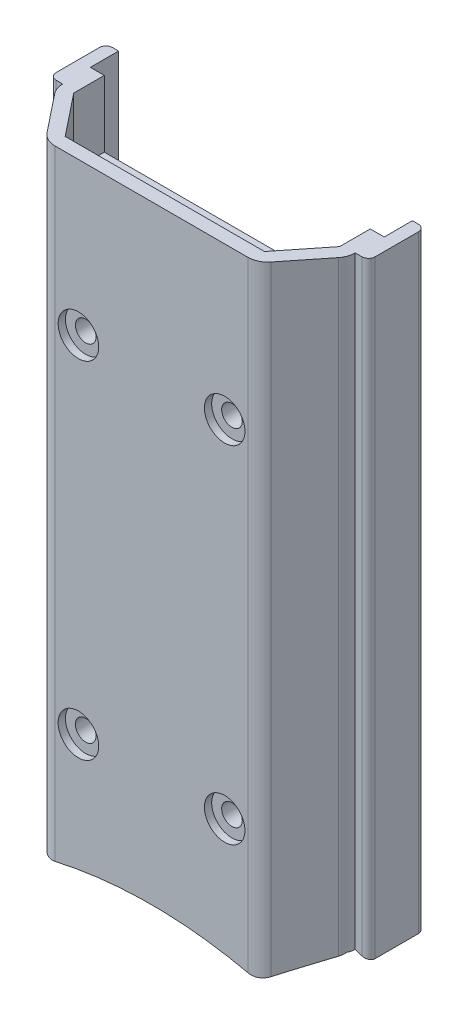
SolidWorks part; units mm, degrees
ref_plane "前视基准面" through (0, 0, 0) normal (0, 0, 1) x (1, 0, 0)
ref_plane "上视基准面" through (0, 0, 0) normal (0, 1, 0) x (1, 0, 0)
ref_plane "右视基准面" through (0, 0, 0) normal (1, 0, 0) x (0, 0, -1)
other "Configuration Table"
sketch "草图1" plane through (0, 0, 0) normal (0, 1, 0) x (1, 0, 0)
  line L5 (21.3466, -10.7196) -> (16.852, -16.3628)
  line L7 (20, -4.6001) -> (22, -4.6001)
  line L9 (20, -9.2001) -> (20, -4.6001)
  line L10 (14.9873, -15.4937) -> (20, -9.2001)
  line L11 (14.5054, -17.4937) -> (-14.5054, -17.4937)
  line L12 (-14.9873, -15.4937) -> (14.9873, -15.4937)
  line L14 (-20, -9.2001) -> (-14.9873, -15.4937)
  line L15 (-20, -4.6001) -> (-20, -9.2001)
  line L17 (-22.1, -0.3496) -> (-23, -0.3496)
  line L18 (-24, -1.3496) -> (-24, -7.8505)
  line L20 (-22, -4.6001) -> (-22.1, -4.6001)
  line L21 (-22.1, -4.6001) -> (-22.1, -0.3496)
  line L22 (22.1, -0.3496) -> (23, -0.3496)
  line L23 (24, -1.3496) -> (24, -7.8505)
  line L41 (22, -4.6001) -> (22.1, -4.6001)
  line L42 (22.1, -4.6001) -> (22.1, -0.3496)
  line L43 (-16.852, -16.3628) -> (-21.3466, -10.7196)
  line L57 (-22, -4.6001) -> (-20, -4.6001)
  line L59 (-22, -8.8505) -> (-23, -8.8505)
  line L61 (22, -8.8505) -> (23, -8.8505)
  arc A2 (23, -8.8505) -> (24, -7.8505) centre (23, -7.8505) ccw
  arc A3 (24, -1.3496) -> (23, -0.3496) centre (23, -1.3496) ccw
  arc A12 (16.852, -16.3628) -> (14.5054, -17.4937) centre (14.5054, -14.4937) cw
  arc A14 (-14.5054, -17.4937) -> (-16.852, -16.3628) centre (-14.5054, -14.4937) cw
  arc A16 (-23, -8.8505) -> (-24, -7.8505) centre (-23, -7.8505) cw
  arc A17 (-23, -0.3496) -> (-24, -1.3496) centre (-23, -1.3496) ccw
  arc A19 (21.3466, -10.7196) -> (22, -8.8505) centre (19, -8.8505) ccw
  arc A20 (-22, -8.8505) -> (-21.3466, -10.7196) centre (-19, -8.8505) ccw
  dimension "D3" = 0.1
  dimension "D2" = 0.1
extrude "凸台-拉伸1" add sketch "草图1" along normal up to surface (58.8974 mm away)
sketch "草图2" plane through (0, 0, 0) normal (0, -1, 0) x (1, 0, 0)
  line L18 (23, 8.8505) -> (22, 8.8505)
  line L19 (-24, 7.8505) -> (-24, 1.3496)
  line L20 (-23, 0.3496) -> (-22.1, 0.3496)
  line L21 (-22.1, 0.3496) -> (-22.1, 4.6001)
  line L22 (-22.1, 4.6001) -> (-20, 4.6001)
  line L23 (-20, 4.6001) -> (-20, 9.2001)
  line L24 (-20, 9.2001) -> (-14.9873, 15.4937)
  line L25 (-14.9873, 15.4937) -> (14.9873, 15.4937)
  line L26 (14.9873, 15.4937) -> (20, 9.2001)
  line L27 (20, 9.2001) -> (20, 4.6001)
  line L28 (20, 4.6001) -> (22.1, 4.6001)
  line L29 (22.1, 4.6001) -> (22.1, 0.3496)
  line L30 (22.1, 0.3496) -> (23, 0.3496)
  line L31 (24, 1.3496) -> (24, 7.8505)
  line L32 (23, 8.8505) -> (22, 8.8505)
  line L33 (21.3466, 10.7196) -> (16.852, 16.3628)
  line L34 (14.5054, 17.4937) -> (-14.5054, 17.4937)
  line L37 (-24, 7.8505) -> (-24, 1.3496)
  line L38 (-23, 0.3496) -> (-22.1, 0.3496)
  line L39 (-22.1, 0.3496) -> (-22.1, 4.6001)
  line L40 (-22.1, 4.6001) -> (-20, 4.6001)
  line L41 (-20, 4.6001) -> (-20, 9.2001)
  line L42 (-20, 9.2001) -> (-14.9873, 15.4937)
  line L43 (-14.9873, 15.4937) -> (14.9873, 15.4937)
  line L44 (14.9873, 15.4937) -> (20, 9.2001)
  line L45 (20, 9.2001) -> (20, 4.6001)
  line L46 (20, 4.6001) -> (22.1, 4.6001)
  line L47 (22.1, 4.6001) -> (22.1, 0.3496)
  line L48 (22.1, 0.3496) -> (23, 0.3496)
  line L49 (24, 1.3496) -> (24, 7.8505)
  line L51 (21.3466, 10.7196) -> (16.852, 16.3628)
  line L52 (14.5054, 17.4937) -> (-14.5054, 17.4937)
  line L57 (-16.852, 16.3628) -> (-21.3466, 10.7196)
  line L58 (-16.852, 16.3628) -> (-21.3466, 10.7196)
  line L61 (-22, 8.8505) -> (-23, 8.8505)
  line L62 (-22, 8.8505) -> (-23, 8.8505)
  arc A8 (-21.3466, 10.7196) -> (-22, 8.8505) centre (-19, 8.8505) ccw
  arc A9 (-21.3466, 10.7196) -> (-22, 8.8505) centre (-19, 8.8505) ccw
  arc A10 (22, 8.8505) -> (21.3466, 10.7196) centre (19, 8.8505) ccw
  arc A11 (22, 8.8505) -> (21.3466, 10.7196) centre (19, 8.8505) ccw
  arc A12 (-23, 8.8505) -> (-24, 7.8505) centre (-23, 7.8505) ccw
  arc A13 (-24, 1.3496) -> (-23, 0.3496) centre (-23, 1.3496) ccw
  arc A14 (23, 0.3496) -> (24, 1.3496) centre (23, 1.3496) ccw
  arc A15 (24, 7.8505) -> (23, 8.8505) centre (23, 7.8505) ccw
  arc A18 (16.852, 16.3628) -> (14.5054, 17.4937) centre (14.5054, 14.4937) ccw
  arc A19 (-14.5054, 17.4937) -> (-16.852, 16.3628) centre (-14.5054, 14.4937) ccw
  arc A22 (-23, 8.8505) -> (-24, 7.8505) centre (-23, 7.8505) ccw
  arc A23 (-24, 1.3496) -> (-23, 0.3496) centre (-23, 1.3496) ccw
  arc A24 (23, 0.3496) -> (24, 1.3496) centre (23, 1.3496) ccw
  arc A25 (24, 7.8505) -> (23, 8.8505) centre (23, 7.8505) ccw
  arc A28 (16.852, 16.3628) -> (14.5054, 17.4937) centre (14.5054, 14.4937) ccw
  arc A29 (-14.5054, 17.4937) -> (-16.852, 16.3628) centre (-14.5054, 14.4937) ccw
  dimension "D1" = 0
extrude "凸台-拉伸2" add sketch "草图2" along normal up to surface (38.3996 mm away)
ref_plane "基准面1" through (0, -38.3996, 0) normal (0, -1, 0) x (-1, 0, 0)
sketch "草图3" plane through (0, 0, 4.6001) normal (0, 0, -1) x (-1, 0, 0)
  line L0 (22.1, -38.3996) -> (22.1, -35.3996)
  line L1 (22.1, 58.8974) -> (22.1, -38.3996) construction
  line L2 (22.1, -35.3996) -> (-22.1, -35.3996)
  line L3 (-22.1, 58.8974) -> (-22.1, -38.3996) construction
  line L4 (-22.1, -35.3996) -> (-22.1, -38.3996)
  line L5 (-22.1, -38.3996) -> (22.1, -38.3996)
  dimension "D1" = 3
extrude "凸台-拉伸3" add sketch "草图3" against normal up to surface (12.8937 mm away) up to face at (0, 10.2489, 17.4937)
sketch "草图4" plane through (0, 0, 4.6001) normal (0, 0, -1) x (-1, 0, 0)
  line L0 (22.1, 38.8974) -> (-22.1, 38.8974)
  line L3 (22.1, 58.8974) -> (22.1, -38.3996) construction
  line L4 (22.1, 38.8974) -> (22.1, 35.8974)
  line L7 (-22.1, 58.8974) -> (-22.1, -38.3996) construction
  line L8 (-22.1, 38.8974) -> (-22.1, 35.8974)
  line L9 (-22.1, 35.8974) -> (22.1, 35.8974)
  dimension "D2" = 3
extrude "凸台-拉伸4" add sketch "草图4" against normal up to surface (12.8937 mm away) up to face at (0, -12.5754, 17.4937)
sketch "草图5" plane through (0, 38.8974, 0) normal (0, 1, 0) x (1, 0, 0)
  line L3 (-22, -8.8505) -> (-22.1, -8.8505)
  line L4 (-22.1, -8.8505) -> (-22.1, -17.4937)
  line L5 (-22.1, -17.4937) -> (-14.5054, -17.4937)
  line L7 (-22.1, -8.8505) -> (-22.1, -17.4937)
  line L8 (-22.1, -17.4937) -> (-14.5054, -17.4937)
  line L9 (14.5054, -17.4937) -> (22.1, -17.4937)
  line L10 (22.1, -17.4937) -> (22.1, -8.8505)
  line L11 (21.3466, -10.7196) -> (16.852, -16.3628)
  line L12 (14.5054, -17.4937) -> (22.1, -17.4937)
  line L13 (22.1, -17.4937) -> (22.1, -8.8505)
  line L14 (21.3466, -10.7196) -> (16.852, -16.3628)
  line L17 (-22, -8.8505) -> (-22.1, -8.8505)
  line L18 (-16.852, -16.3628) -> (-21.3466, -10.7196)
  line L19 (-16.852, -16.3628) -> (-21.3466, -10.7196)
  line L22 (22.1, -8.8505) -> (22, -8.8505)
  line L23 (22.1, -8.8505) -> (22, -8.8505)
  arc A2 (-22, -8.8505) -> (-21.3466, -10.7196) centre (-19, -8.8505) ccw
  arc A3 (-16.852, -16.3628) -> (-14.5054, -17.4937) centre (-14.5054, -14.4937) ccw
  arc A4 (-22, -8.8505) -> (-21.3466, -10.7196) centre (-19, -8.8505) ccw
  arc A5 (21.3466, -10.7196) -> (22, -8.8505) centre (19, -8.8505) ccw
  arc A6 (-16.852, -16.3628) -> (-14.5054, -17.4937) centre (-14.5054, -14.4937) ccw
  arc A9 (14.5054, -17.4937) -> (16.852, -16.3628) centre (14.5054, -14.4937) ccw
  arc A10 (21.3466, -10.7196) -> (22, -8.8505) centre (19, -8.8505) ccw
  arc A12 (14.5054, -17.4937) -> (16.852, -16.3628) centre (14.5054, -14.4937) ccw
  dimension "D1" = 0
  dimension "D2" = 0
extrude "切除-拉伸1" cut sketch "草图5" against normal up to surface (77.297 mm away) contours A6 L8 L7 L17 A4 L19 | A12 L14 A10 L23 L13 L12 up to face at (0, -38.3996, 6.2118)
sketch "草图6" plane through (0, 38.8974, 0) normal (0, 1, 0) x (1, 0, 0)
  line L12 (8.0613, -11.7949) -> (8.0613, -7.4001)
  line L13 (8.0613, -7.4001) -> (-8.0613, -7.4001)
  line L14 (-8.0613, -7.4001) -> (-8.0613, -11.7949)
  line L15 (-8.0613, -11.7949) -> (8.0613, -11.7949)
extrude "切除-拉伸2" cut sketch "草图6" against normal up to surface (3 mm away) up to face at (0, 35.8974, 9.7646)
sketch "草图7" plane through (0, -38.3996, 0) normal (0, -1, 0) x (-1, 0, 0)
  line L20 (20, -4.6001) -> (20, -9.2001)
  line L21 (22, -4.6001) -> (20, -4.6001)
  line L22 (22.1, -4.6001) -> (22, -4.6001)
  line L23 (22.1, -0.3496) -> (22.1, -4.6001)
  line L24 (23, -0.3496) -> (22.1, -0.3496)
  line L25 (24, -7.8505) -> (24, -1.3496)
  line L26 (22, -8.8505) -> (23, -8.8505)
  line L27 (16.852, -16.3628) -> (21.3466, -10.7196)
  line L28 (-14.5054, -17.4937) -> (14.5054, -17.4937)
  line L29 (-21.3466, -10.7196) -> (-16.852, -16.3628)
  line L30 (-23, -8.8505) -> (-22, -8.8505)
  line L31 (-24, -1.3496) -> (-24, -7.8505)
  line L32 (-22.1, -0.3496) -> (-23, -0.3496)
  line L33 (-22.1, -4.6001) -> (-22.1, -0.3496)
  line L34 (-22, -4.6001) -> (-22.1, -4.6001)
  line L35 (-20, -4.6001) -> (-22, -4.6001)
  line L36 (-20, -9.2001) -> (-20, -4.6001)
  line L37 (-14.9873, -15.4937) -> (-20, -9.2001)
  line L38 (14.9873, -15.4937) -> (-14.9873, -15.4937)
  line L39 (20, -9.2001) -> (14.9873, -15.4937)
  line L40 (20, -4.6001) -> (20, -9.2001)
  line L41 (22, -4.6001) -> (20, -4.6001)
  line L42 (22.1, -4.6001) -> (22, -4.6001)
  line L43 (22.1, -0.3496) -> (22.1, -4.6001)
  line L44 (23, -0.3496) -> (22.1, -0.3496)
  line L45 (24, -7.8505) -> (24, -1.3496)
  line L46 (22, -8.8505) -> (23, -8.8505)
  line L47 (16.852, -16.3628) -> (21.3466, -10.7196)
  line L48 (-14.5054, -17.4937) -> (14.5054, -17.4937)
  line L49 (-21.3466, -10.7196) -> (-16.852, -16.3628)
  line L50 (-23, -8.8505) -> (-22, -8.8505)
  line L51 (-24, -1.3496) -> (-24, -7.8505)
  line L52 (-22.1, -0.3496) -> (-23, -0.3496)
  line L53 (-22.1, -4.6001) -> (-22.1, -0.3496)
  line L54 (-22, -4.6001) -> (-22.1, -4.6001)
  line L55 (-20, -4.6001) -> (-22, -4.6001)
  line L56 (-20, -9.2001) -> (-20, -4.6001)
  line L57 (-14.9873, -15.4937) -> (-20, -9.2001)
  line L58 (14.9873, -15.4937) -> (-14.9873, -15.4937)
  line L59 (20, -9.2001) -> (14.9873, -15.4937)
  arc A8 (24, -1.3496) -> (23, -0.3496) centre (23, -1.3496) ccw
  arc A9 (23, -8.8505) -> (24, -7.8505) centre (23, -7.8505) ccw
  arc A10 (21.3466, -10.7196) -> (22, -8.8505) centre (19, -8.8505) ccw
  arc A11 (14.5054, -17.4937) -> (16.852, -16.3628) centre (14.5054, -14.4937) ccw
  arc A12 (-16.852, -16.3628) -> (-14.5054, -17.4937) centre (-14.5054, -14.4937) ccw
  arc A13 (-22, -8.8505) -> (-21.3466, -10.7196) centre (-19, -8.8505) ccw
  arc A14 (-24, -7.8505) -> (-23, -8.8505) centre (-23, -7.8505) ccw
  arc A15 (-23, -0.3496) -> (-24, -1.3496) centre (-23, -1.3496) ccw
  arc A16 (24, -1.3496) -> (23, -0.3496) centre (23, -1.3496) ccw
  arc A17 (23, -8.8505) -> (24, -7.8505) centre (23, -7.8505) ccw
  arc A18 (21.3466, -10.7196) -> (22, -8.8505) centre (19, -8.8505) ccw
  arc A19 (14.5054, -17.4937) -> (16.852, -16.3628) centre (14.5054, -14.4937) ccw
  arc A20 (-16.852, -16.3628) -> (-14.5054, -17.4937) centre (-14.5054, -14.4937) ccw
  arc A21 (-22, -8.8505) -> (-21.3466, -10.7196) centre (-19, -8.8505) ccw
  arc A22 (-24, -7.8505) -> (-23, -8.8505) centre (-23, -7.8505) ccw
  arc A23 (-23, -0.3496) -> (-24, -1.3496) centre (-23, -1.3496) ccw
  dimension "D1" = 0
extrude "凸台-拉伸5" add sketch "草图7" along normal blind 15
sketch "草图8" plane through (0, 0, 0) normal (1, 0, 0) x (0, 0, -1)
  line L14 (-9.8992, -38.2996) -> (-20.2915, -44.2996)
  line L18 (-9.8992, -40.3996) -> (-9.8992, -176.3996) construction
  line L19 (-20.2915, -44.3996) -> (-20.2915, -172.3996) construction
  line L20 (-20.2915, -44.2996) -> (-20.2915, -55.8019)
  line L21 (-9.8992, -108.3996) -> (14.8215, -108.3996) construction
  line L22 (-20.2915, -46.3996) -> (-20.2915, -170.3996) construction
  line L23 (-20.2915, -55.8019) -> (11.0914, -55.8019)
  line L25 (0.6991, -38.2996) -> (-9.8992, -38.2996)
  line L26 (-4.6001, 35.8974) -> (-4.6001, -35.3996) construction
  line L27 (11.0914, -44.2996) -> (11.0914, -55.8019)
  line L28 (0.6991, -38.2996) -> (11.0914, -44.2996)
revolve "切除-旋转1" cut sketch "草图8" angle 360 about L21
sketch "草图9" plane through (0, 0, 15.4937) normal (0, 0, -1) x (-1, 0, 0)
  circle A1 centre (-11, 26.0001) radius 3.5
  circle A2 centre (11, 26.0001) radius 3.5
  circle A3 centre (-11, -26.0001) radius 3.5
  circle A4 centre (11, -26.0001) radius 3.5
extrude "凸台-拉伸6" add sketch "草图9" along normal blind 6.3
sketch "草图10" plane through (0, 0, 9.1937) normal (0, 0, -1) x (-1, 0, 0)
  circle A0 centre (-11, 26.0001) radius 1.55
  circle A1 centre (11, 26.0001) radius 1.55
  circle A2 centre (-11, -26.0001) radius 1.55
  circle A3 centre (11, -26.0001) radius 1.55
extrude "切除-拉伸3" cut sketch "草图10" against normal through all and the other way through all
sketch "草图11" plane through (0, 0, 17.4937) normal (0, 0, 1) x (1, 0, 0)
  circle A0 centre (-11, 26.0001) radius 3.05
  circle A1 centre (11, 26.0001) radius 3.05
  circle A2 centre (-11, -26.0001) radius 3.05
  circle A3 centre (11, -26.0001) radius 3.05
extrude "切除-拉伸4" cut sketch "草图11" against normal blind 1.1
sketch "草图13" plane through (0, 58.8974, 0) normal (0, 1, 0) x (1, 0, 0)
  line L18 (-23, -8.8505) -> (-22, -8.8505)
  line L19 (-21.3466, -10.7196) -> (-16.852, -16.3628)
  line L20 (-14.5054, -17.4937) -> (14.5054, -17.4937)
  line L21 (16.852, -16.3628) -> (21.3466, -10.7196)
  line L22 (22, -8.8505) -> (23, -8.8505)
  line L23 (24, -7.8505) -> (24, -1.3496)
  line L24 (23, -0.3496) -> (22.1, -0.3496)
  line L25 (22.1, -0.3496) -> (22.1, -4.6001)
  line L26 (22.1, -4.6001) -> (20, -4.6001)
  line L27 (20, -4.6001) -> (20, -9.2001)
  line L28 (20, -9.2001) -> (14.9873, -15.4937)
  line L29 (14.9873, -15.4937) -> (-14.9873, -15.4937)
  line L30 (-14.9873, -15.4937) -> (-20, -9.2001)
  line L31 (-20, -9.2001) -> (-20, -4.6001)
  line L32 (-20, -4.6001) -> (-22.1, -4.6001)
  line L33 (-22.1, -4.6001) -> (-22.1, -0.3496)
  line L34 (-22.1, -0.3496) -> (-23, -0.3496)
  line L35 (-24, -1.3496) -> (-24, -7.8505)
  line L36 (-23, -8.8505) -> (-22, -8.8505)
  line L37 (-21.3466, -10.7196) -> (-16.852, -16.3628)
  line L38 (-14.5054, -17.4937) -> (14.5054, -17.4937)
  line L39 (16.852, -16.3628) -> (21.3466, -10.7196)
  line L40 (22, -8.8505) -> (23, -8.8505)
  line L41 (24, -7.8505) -> (24, -1.3496)
  line L42 (23, -0.3496) -> (22.1, -0.3496)
  line L43 (22.1, -0.3496) -> (22.1, -4.6001)
  line L44 (22.1, -4.6001) -> (20, -4.6001)
  line L45 (20, -4.6001) -> (20, -9.2001)
  line L46 (20, -9.2001) -> (14.9873, -15.4937)
  line L47 (14.9873, -15.4937) -> (-14.9873, -15.4937)
  line L48 (-14.9873, -15.4937) -> (-20, -9.2001)
  line L49 (-20, -9.2001) -> (-20, -4.6001)
  line L50 (-20, -4.6001) -> (-22.1, -4.6001)
  line L51 (-22.1, -4.6001) -> (-22.1, -0.3496)
  line L52 (-22.1, -0.3496) -> (-23, -0.3496)
  line L53 (-24, -1.3496) -> (-24, -7.8505)
  arc A8 (-22, -8.8505) -> (-21.3466, -10.7196) centre (-19, -8.8505) ccw
  arc A9 (-16.852, -16.3628) -> (-14.5054, -17.4937) centre (-14.5054, -14.4937) ccw
  arc A10 (14.5054, -17.4937) -> (16.852, -16.3628) centre (14.5054, -14.4937) ccw
  arc A11 (21.3466, -10.7196) -> (22, -8.8505) centre (19, -8.8505) ccw
  arc A12 (23, -8.8505) -> (24, -7.8505) centre (23, -7.8505) ccw
  arc A13 (24, -1.3496) -> (23, -0.3496) centre (23, -1.3496) ccw
  arc A14 (-23, -0.3496) -> (-24, -1.3496) centre (-23, -1.3496) ccw
  arc A15 (-24, -7.8505) -> (-23, -8.8505) centre (-23, -7.8505) ccw
  arc A16 (-22, -8.8505) -> (-21.3466, -10.7196) centre (-19, -8.8505) ccw
  arc A17 (-16.852, -16.3628) -> (-14.5054, -17.4937) centre (-14.5054, -14.4937) ccw
  arc A18 (14.5054, -17.4937) -> (16.852, -16.3628) centre (14.5054, -14.4937) ccw
  arc A19 (21.3466, -10.7196) -> (22, -8.8505) centre (19, -8.8505) ccw
  arc A20 (23, -8.8505) -> (24, -7.8505) centre (23, -7.8505) ccw
  arc A21 (24, -1.3496) -> (23, -0.3496) centre (23, -1.3496) ccw
  arc A22 (-23, -0.3496) -> (-24, -1.3496) centre (-23, -1.3496) ccw
  arc A23 (-24, -7.8505) -> (-23, -8.8505) centre (-23, -7.8505) ccw
  dimension "D1" = 0
extrude "切除-拉伸5" cut sketch "草图13" against normal blind 10
